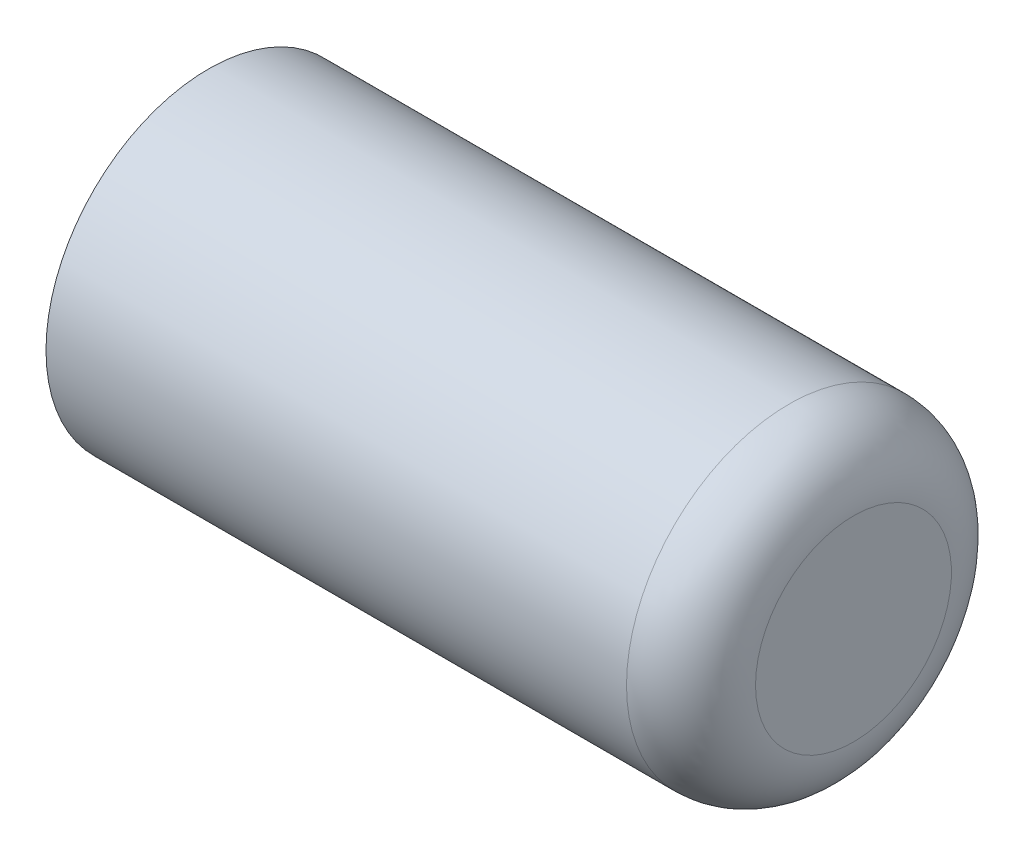
SolidWorks part; units mm, degrees
ref_plane "Front Plane" through (0, 0, 0) normal (0, 0, 1) x (1, 0, 0)
ref_plane "Top Plane" through (0, 0, 0) normal (0, 1, 0) x (1, 0, 0)
ref_plane "Right Plane" through (0, 0, 0) normal (1, 0, 0) x (0, 0, -1)
sketch "Sketch1" plane through (0, 0, 0) normal (0, 0, 1) x (1, 0, 0)
  line L0 (0, 0) -> (382.4174, 0) construction
  line L1 (0, 0) -> (0, 76.2) construction
  line L2 (-127, 76.2) -> (101.6, 177.8)
  line L3 (127, 177.8) -> (127, 127)
  line L4 (127, 127) -> (101.6, 127)
  line L5 (101.6, 127) -> (101.6, 126.746)
  line L6 (76.454, 101.6) -> (-76.454, 101.6)
  line L8 (-127, 76.2) -> (-127, 127)
  line L9 (-127, 127) -> (-101.6, 127)
  line L10 (0, 101.6) -> (0, 292.5272) construction
  line L11 (0, 101.6) -> (0, 76.2) construction
  line L12 (0, 38.1) -> (0, 63.9768)
  line L13 (-101.6, 127) -> (-101.6, 126.746)
  arc A0 (101.6, 126.746) -> (76.454, 101.6) centre (76.454, 126.746) cw
  arc A1 (-101.6, 126.746) -> (-76.454, 101.6) centre (-76.454, 126.746) ccw
  spline S0 degree 3 poles (127, 177.8) (127, 109.2815) (62.7137, 48.9792) (0, 38.1) knots 0 0 0 0 1 1 1 1
  spline S1 degree 1 poles (101.6, 177.8) (-4.3414, 63.1262) knots 0 0 1 1 construction
  spline S2 degree 3 poles (101.6, 177.8) (101.6, 171.2339) (100.0647, 158.1657) (93.4954, 138.9502) (82.9987, 120.5216) (69.1088, 103.539) (52.5355, 88.6704) (37.1829, 78.56) (24.44, 72.1043) (14.7724, 68.1317) (6.7369, 65.5853) (0.362, 64.0187) (-2.7614, 63.4003) (-4.3414, 63.1262) knots 0 0 0 0 0.125 0.25 0.375 0.5 0.625 0.75 0.8125 0.875 0.9375 0.96875 1 1 1 1 only from (101.6, 177.8) to (0, 63.9768)
  dimension "D6" = 25.146
  dimension "D1" = 127
  dimension "D2" = 50.8
  dimension "D3" = 25.4
  dimension "D4" = 25.4
  dimension "D5" = 101.6
  dimension "D7" = 38.1
  dimension "D8" = 76.2
  dimension "D9" = 25.4
revolve "Revolve1" add sketch "Sketch1" angle 360 about L0 rebuild error yes
sketch "Sketch4" plane through (-127, 0, 0) normal (-1, 0, 0) x (0, 0, 1)
  circle A0 centre (0, 0) radius 38.1 construction
  circle A1 centre (0, 0) radius 38.1
  circle A2 centre (0, 0) radius 63.9768 construction
  circle A3 centre (0, 0) radius 63.9768
extrude "Boss-Extrude1" add sketch "Sketch4" against normal blind 254
sketch "Sketch5" plane through (127, 0, 0) normal (1, 0, 0) x (0, 0, -1)
  circle A0 centre (0, 0) radius 63.9768 construction
  circle A1 centre (0, 0) radius 63.9768
extrude "Boss-Extrude2" add sketch "Sketch5" against normal blind 50.8
sketch "Sketch6" plane through (127, 0, 0) normal (1, 0, 0) x (0, 0, -1)
  line L0 (-18.2791, 61.3099) -> (-50.8, 170.3884)
  line L3 (18.2791, 61.3099) -> (50.8, 170.3884)
  circle A0 centre (0, 0) radius 177.8 construction
  arc A1 (50.8, 170.3884) -> (-50.8, 170.3884) centre (0, 0) ccw
  circle A2 centre (0, 0) radius 63.9768 construction
  arc A3 (18.2791, 61.3099) -> (-18.2791, 61.3099) centre (0, 0) ccw
  point P8 (0, 0)
  dimension "D1" = 101.6
extrude "Cut-Extrude1" cut sketch "Sketch6" against normal through all rebuild error yes
pattern_circular "CirPattern1" count 6 over 360 rebuild error yes
fillet "Fillet2" radius 25.4 1 edges at (127, 0, 63.9768)
